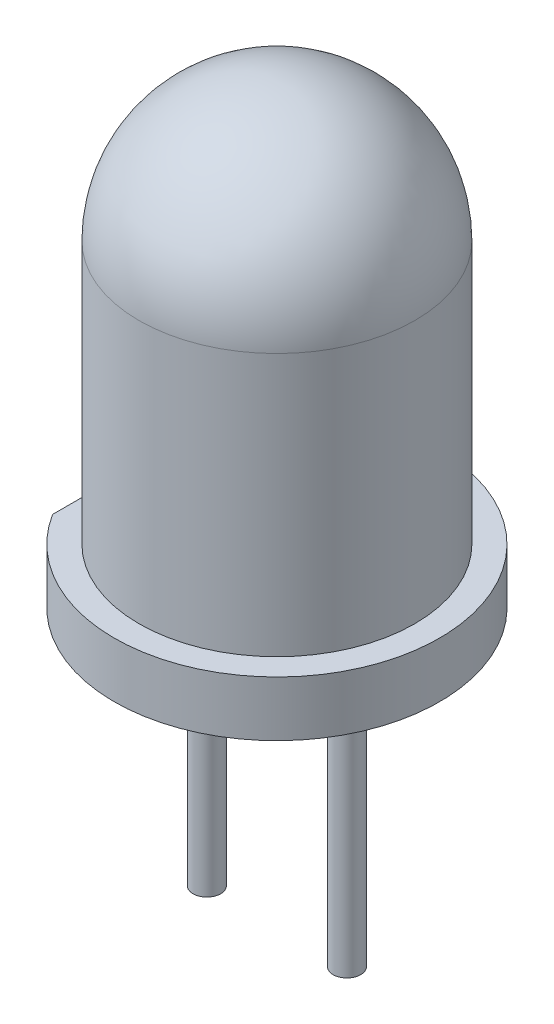
SolidWorks part; units mm, degrees
ref_plane "Alzado" through (0, 0, 0) normal (0, 0, 1) x (1, 0, 0)
ref_plane "Planta" through (0, 0, 0) normal (0, 1, 0) x (1, 0, 0)
ref_plane "Vista lateral" through (0, 0, 0) normal (1, 0, 0) x (0, 0, -1)
sketch "Sketch1" plane through (0, 0, 0) normal (0, 1, 0) x (1, 0, 0)
  circle A0 centre (0, 0) radius 2.95
  dimension "D1" = 2.95
extrude "Boss-Extrude1" add sketch "Sketch1" along normal blind 1
sketch "Sketch2" plane through (0, 1, 0) normal (0, 1, 0) x (1, 0, 0)
  circle A0 centre (0, 0) radius 2.5
  dimension "D1" = 5
extrude "Boss-Extrude2" add sketch "Sketch2" along normal blind 4.76 contours A0
sketch "Sketch3" plane through (0, 1, 0) normal (0, 1, 0) x (1, 0, 0)
  line L0 (-2.5, 1.566) -> (-2.5, -1.566)
  circle A0 centre (0, 0) radius 2.95 construction
  circle A1 centre (0, 0) radius 2.5 construction
  arc A2 (-2.5, 1.566) -> (-2.5, -1.566) centre (0, 0) ccw
extrude "Cut-Extrude1" cut sketch "Sketch3" against normal through all
sketch "Sketch4" plane through (0, 5.76, 0) normal (0, -1, 0) x (1, 0, 0)
  line L0 (0, -2.5) -> (0, 2.5)
  circle A0 centre (0, 0) radius 2.5 construction
  circle A1 centre (0, 0) radius 2.5 construction
  arc A2 (0, -2.5) -> (0, 2.5) centre (0, 0) ccw
revolve "Revolve1" add sketch "Sketch4" angle 360 about L0
sketch "Sketch5" plane through (0, 0, 0) normal (0, -1, 0) x (1, 0, 0)
  line L0 (-1.27, 0) -> (0, 0) construction
  line L1 (0, 0) -> (1.27, 0) construction
  circle A0 centre (1.27, 0) radius 0.25
  circle A1 centre (-1.27, 0) radius 0.25
  dimension "D1" = 2.54
  dimension "D2" = 0.5
extrude "Boss-Extrude3" add sketch "Sketch5" along normal blind 5
